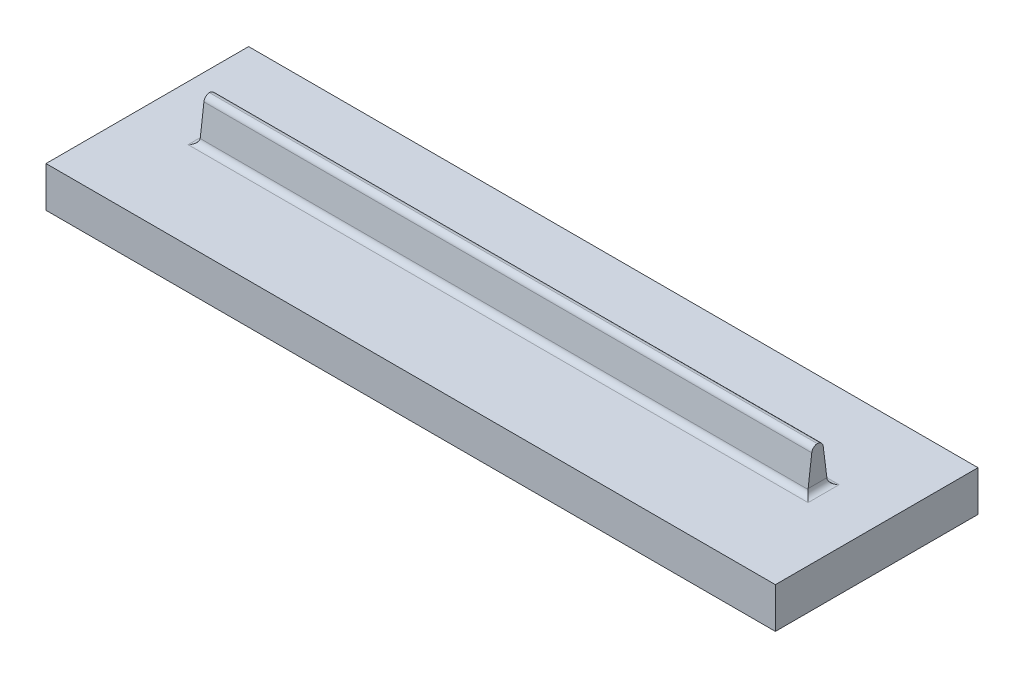
SolidWorks part; units mm, degrees
ref_plane "Front Plane" through (0, 0, 0) normal (0, 0, 1) x (1, 0, 0)
ref_plane "Top Plane" through (0, 0, 0) normal (0, 1, 0) x (1, 0, 0)
ref_plane "Right Plane" through (0, 0, 0) normal (1, 0, 0) x (0, 0, -1)
sketch "Sketch1" plane through (0, 0, 0) normal (0, 1, 0) x (1, 0, 0)
  line L1 (-52.6246, 25.9136) -> (127.3754, 25.9136)
  line L2 (-52.6246, 25.9136) -> (-52.6246, -24.0864)
  line L3 (-52.6246, -24.0864) -> (127.3754, -24.0864)
  line L4 (127.3754, 25.9136) -> (127.3754, -24.0864)
  dimension "D1" = 180
  dimension "D2" = 50
extrude "Boss-Extrude1" add sketch "Sketch1" along normal blind 10
sketch "Sketch3" plane through (127.3754, 0, 0) normal (1, 0, 0) x (0, 0, -1)
  line L1 (-24.0864, 10) -> (25.9136, 10) construction
  line L2 (-1.1964, 10) -> (3.8036, 10)
  line L4 (0.0536, 20) -> (2.5536, 20)
  line L5 (0.0536, 20) -> (-1.1964, 10)
  line L6 (2.5536, 20) -> (3.8036, 10)
  dimension "D1" = 22.89
  dimension "D2" = 5
  dimension "D4" = 2.5
extrude "Boss-Extrude2" add sketch "Sketch3" against normal blind 180
sketch "Sketch4" plane through (127.3754, 0, 0) normal (1, 0, 0) x (0, 0, -1)
  line L0 (-8.2254, 23.2643) -> (12.9447, 23.2643)
  line L1 (-8.2254, 23.2643) -> (-8.2254, 10)
  line L2 (-24.0864, 10) -> (-1.1964, 10) construction
  line L3 (-8.2254, 10) -> (12.9447, 10)
  line L4 (3.8036, 10) -> (25.9136, 10) construction
  line L5 (12.9447, 23.2643) -> (12.9447, 10)
extrude "Cut-Extrude1" cut sketch "Sketch4" against normal blind 15
sketch "Sketch5" plane through (-52.6246, 0, 0) normal (-1, 0, 0) x (0, 0, 1)
  line L0 (-13.4619, 23.2643) -> (7.7082, 23.2643)
  line L1 (-13.4619, 23.2643) -> (-13.4619, 10)
  line L2 (-13.4619, 10) -> (7.7082, 10)
  line L3 (7.7082, 23.2643) -> (7.7082, 10)
  line L4 (1.1964, 10) -> (24.0864, 10) construction
extrude "Cut-Extrude2" cut sketch "Sketch5" against normal blind 15
fillet "Fillet1" radius 1.5 1 edges at (37.3754, 20, -2.5536)
fillet "Fillet2" radius 1.5 1 edges at (37.3754, 20, -0.0536)
fillet "Fillet3" radius 1.5 1 edges at (37.3754, 10, 1.1964)
fillet "Fillet4" radius 1.5 1 edges at (-37.6246, 10, -0.6415)
fillet "Fillet5" radius 1.5 1 edges at (36.6254, 10, -3.8036)
fillet "Fillet6" radius 1.5 1 edges at (112.3754, 10, -1.3036)
